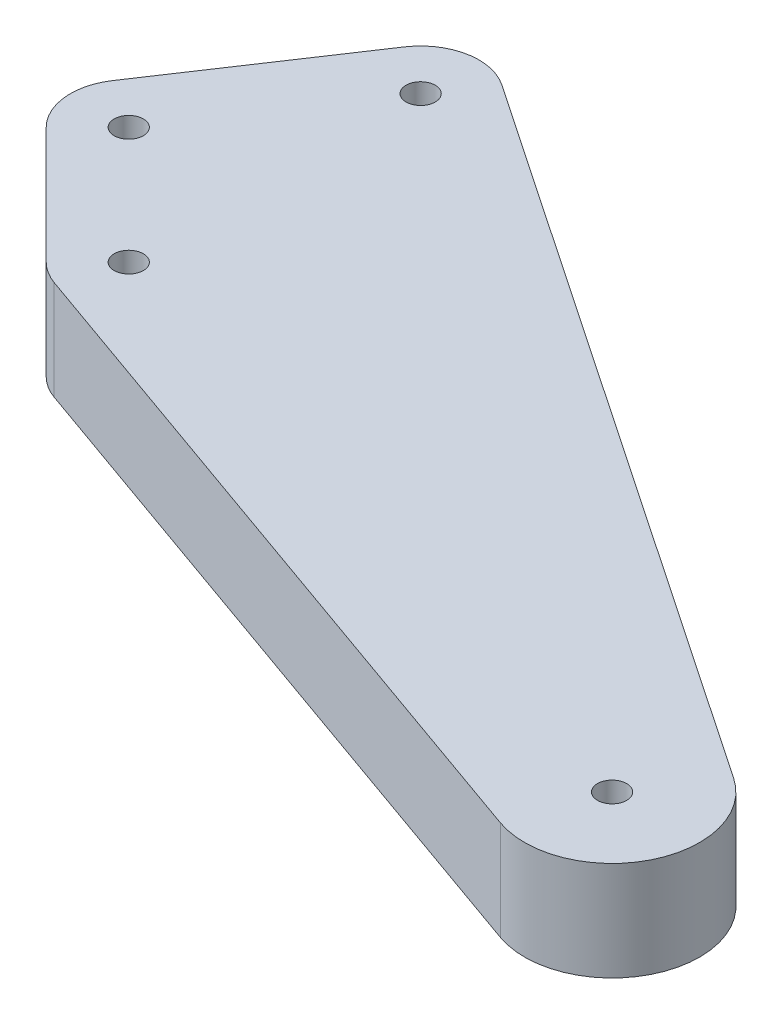
SolidWorks part; units mm, degrees
ref_plane "Front Plane" through (0, 0, 0) normal (0, 0, 1) x (1, 0, 0)
ref_plane "Top Plane" through (0, 0, 0) normal (0, 1, 0) x (1, 0, 0)
ref_plane "Right Plane" through (0, 0, 0) normal (1, 0, 0) x (0, 0, -1)
sketch "Sketch1" plane through (0, 0, 0) normal (0, 1, 0) x (1, 0, 0)
  line L1 (5.6025, 58.2832) -> (128.4037, -24.7751)
  line L2 (114.9918, -51.3392) -> (-3.3388, -9.4262)
  line L4 (-8.3205, 55.547) -> (-28.3205, 25.547)
  line L5 (-27.0711, 12.9289) -> (-7.0711, -7.0711)
  arc A0 (-8.3205, 55.547) -> (5.6025, 58.2832) centre (0, 50) cw
  arc A1 (128.4037, -24.7751) -> (114.9918, -51.3392) centre (120, -37.2) cw
  arc A2 (-3.3388, -9.4262) -> (-7.0711, -7.0711) centre (0, 0) cw
  arc A3 (-28.3205, 25.547) -> (-27.0711, 12.9289) centre (-20, 20) ccw
  dimension "D1" = 10
  dimension "D2" = 10
  dimension "D3" = 15
  dimension "D9" = 10
  dimension "D4" = 87.2
  dimension "D5" = 50
  dimension "D6" = 120
  dimension "D7" = 20
  dimension "D8" = 30
extrude "Boss-Extrude1" add sketch "Sketch1" along normal blind 17
sketch "Sketch2" plane through (0, 17, 0) normal (0, 1, 0) x (1, 0, 0)
  circle A0 centre (0, 50) radius 2.5
  circle A1 centre (0, 0) radius 2.5
  circle A2 centre (120, -37.2) radius 2.5
  circle A3 centre (-20, 20) radius 2.5
  arc A4 (-28.3205, 25.547) -> (-27.0711, 12.9289) centre (-20, 20) ccw construction
  dimension "D1" = 5
  dimension "D2" = 5
extrude "Cut-Extrude1" cut sketch "Sketch2" against normal through all
